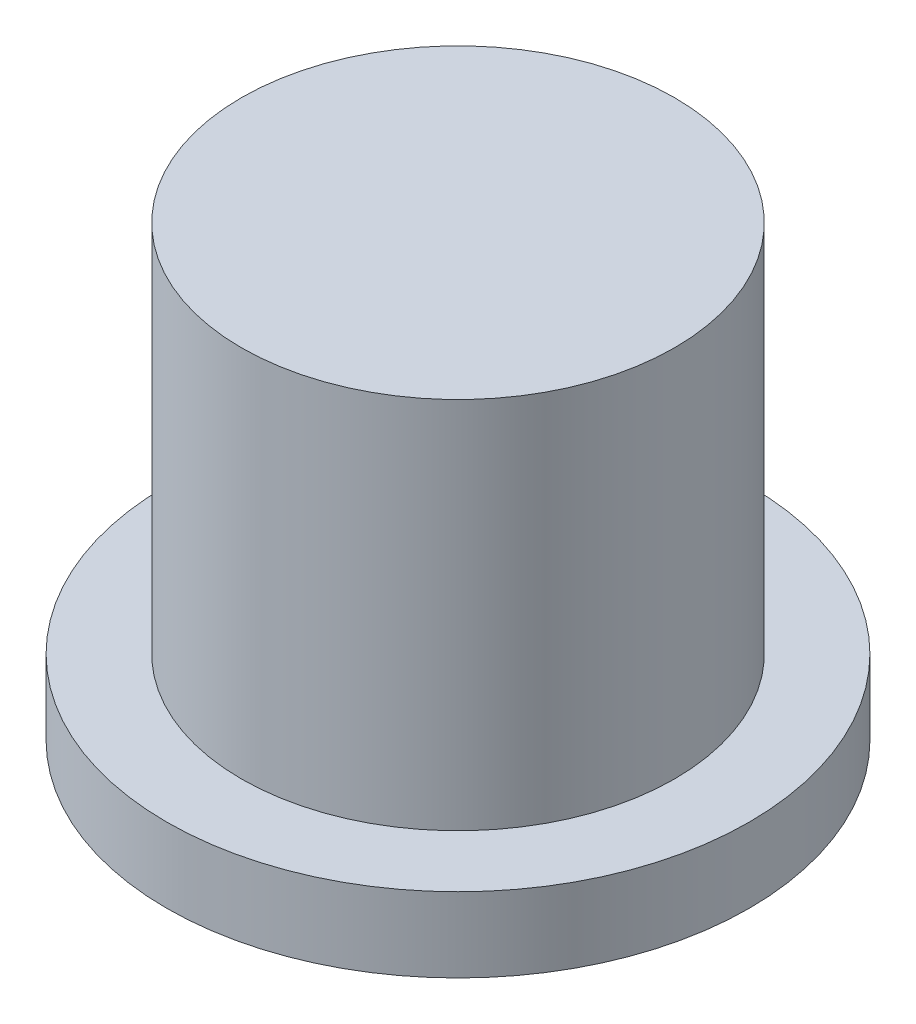
SolidWorks part; units mm, degrees
ref_plane "前视基准面" through (0, 0, 0) normal (0, 0, 1) x (1, 0, 0)
ref_plane "上视基准面" through (0, 0, 0) normal (0, 1, 0) x (1, 0, 0)
ref_plane "右视基准面" through (0, 0, 0) normal (1, 0, 0) x (0, 0, -1)
other "Configuration Table"
sketch "草图1" plane through (0, 0, 0) normal (0, 1, 0) x (1, 0, 0)
  circle A0 centre (0, 0) radius 2.9
  circle A1 centre (0, 0) radius 1.9
  circle A2 centre (0, 0) radius 3.9
  dimension "D1" = 3.8
  dimension "D2" = 1
  dimension "D3" = 1
extrude "凸台-拉伸1" add sketch "草图1" along normal blind 5 contours A0 | A1
extrude "凸台-拉伸2" add sketch "草图1<7>" along normal blind 1 from surface contours A0 starting at face at (0, 5, 2.9)
sketch "草图1<7>" plane through (0, 0, 0) normal (0, 1, 0) x (1, 0, 0) same geometry as "草图1"
extrude "凸台-拉伸3" add sketch "草图1<8>" along normal blind 1 contours A2 | A1
sketch "草图1<8>" plane through (0, 0, 0) normal (0, 1, 0) x (1, 0, 0) same geometry as "草图1"
